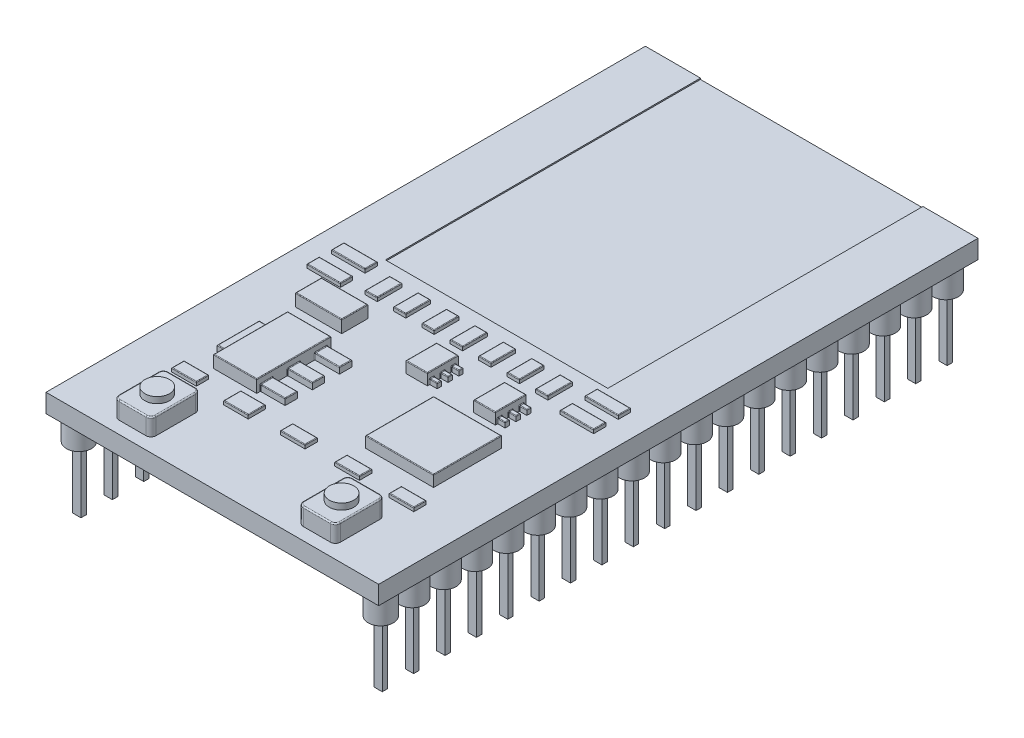
SolidWorks part; units mm, degrees
other "Markup1"
sketch "Sketch18" plane through (14.25, -8, 25.25) normal (0.0351, -0.9994, 0.0068) x (-0.8094, -0.0324, -0.5863)
sketch "Sketch19" plane through (14.25, -8, 25.25) normal (0.0351, -0.9994, 0.0068) x (-0.8094, -0.0324, -0.5863)
ref_plane "Alzado" through (0, 0, 0) normal (0, 0, 1) x (1, 0, 0)
ref_plane "Planta" through (0, 0, 0) normal (0, 1, 0) x (1, 0, 0)
ref_plane "Vista lateral" through (0, 0, 0) normal (1, 0, 0) x (0, 0, -1)
sketch "Sketch1" plane through (0, 0, 0) normal (0, 1, 0) x (1, 0, 0)
  line L0 (0, 0) -> (0, 24.257) construction
  line L1 (13.462, -24.257) -> (-13.462, -24.257)
  line L2 (13.462, -24.257) -> (13.462, 24.257)
  line L3 (13.462, 24.257) -> (-13.462, 24.257)
  line L4 (-13.462, -24.257) -> (-13.462, 24.257)
  line L5 (13.462, -24.257) -> (-13.462, 24.257) construction
  line L6 (13.462, 24.257) -> (-13.462, -24.257) construction
  line L7 (13.462, 0) -> (-13.462, 0) construction
  line L12 (11.462, 24.257) -> (11.462, 22.257) construction
  point P0 (0, 0)
  point P6 (13.462, 23.257)
  point P7 (12.462, 24.257)
  point P8 (17.05, 25.3)
  point P29 (11.462, 24.257)
  point P30 (-13.462, 24.257)
  point P31 (13.462, 24.257)
  point P32 (13.462, -24.257)
  point P33 (-13.462, -24.257)
  dimension "D1" = 48.514
  dimension "D2" = 26.924
  dimension "D3" = 1
  dimension "D4" = 1
  dimension "D6" = 2
  dimension "D7" = 2
extrude "Boss-Extrude1" add sketch "Sketch1" along normal blind 1.5 contours L1 L2 L3 L4 region at (0, 0, 0)
sketch "Sketch2" plane through (0, 0, 0) normal (0, -1, 0) x (1, 0, 0)
  line L0 (0, -24.257) -> (0, 24.257) construction
  line L1 (13.462, -24.257) -> (-13.462, -24.257) construction
  line L2 (13.462, 24.257) -> (-13.462, 24.257) construction
  line L3 (13.462, 0) -> (-13.462, 0) construction
  line L4 (13.462, 24.257) -> (13.462, -24.257) construction
  line L5 (-13.462, 24.257) -> (-13.462, -24.257) construction
  line L6 (-12.962, -23.0261) -> (-12.962, 24.257) construction
  line L7 (-12.962, -23.0261) -> (-12.962, -24.257) construction
  line L8 (-12.812, -19.067) -> (-12.712, -18.967)
  line L9 (-13.112, -18.567) -> (-12.812, -18.567)
  line L10 (-13.212, -18.667) -> (-13.212, -18.967)
  line L11 (-13.112, -19.067) -> (-12.812, -19.067)
  line L12 (-12.712, -18.667) -> (-12.712, -18.967)
  line L13 (-13.212, -18.567) -> (-12.712, -19.067) construction
  line L14 (-13.212, -19.067) -> (-12.712, -18.567) construction
  line L15 (-13.212, -18.967) -> (-13.112, -19.067)
  line L16 (-13.212, -18.667) -> (-13.112, -18.567)
  line L17 (-12.812, -18.567) -> (-12.712, -18.667)
  line L18 (-13.212, -16.427) -> (-13.112, -16.527)
  line L19 (-13.112, -16.527) -> (-12.812, -16.527)
  line L20 (-12.812, -16.527) -> (-12.712, -16.427)
  line L21 (-12.712, -16.127) -> (-12.712, -16.427)
  line L22 (-12.812, -16.027) -> (-12.712, -16.127)
  line L23 (-13.112, -16.027) -> (-12.812, -16.027)
  line L24 (-13.212, -16.127) -> (-13.112, -16.027)
  line L25 (-13.212, -16.127) -> (-13.212, -16.427)
  line L26 (-13.212, -13.887) -> (-13.112, -13.987)
  line L27 (-13.112, -13.987) -> (-12.812, -13.987)
  line L28 (-12.812, -13.987) -> (-12.712, -13.887)
  line L29 (-12.712, -13.587) -> (-12.712, -13.887)
  line L30 (-12.812, -13.487) -> (-12.712, -13.587)
  line L31 (-13.112, -13.487) -> (-12.812, -13.487)
  line L32 (-13.212, -13.587) -> (-13.112, -13.487)
  line L33 (-13.212, -13.587) -> (-13.212, -13.887)
  line L34 (-13.212, -11.347) -> (-13.112, -11.447)
  line L35 (-13.112, -11.447) -> (-12.812, -11.447)
  line L36 (-12.812, -11.447) -> (-12.712, -11.347)
  line L37 (-12.712, -11.047) -> (-12.712, -11.347)
  line L38 (-12.812, -10.947) -> (-12.712, -11.047)
  line L39 (-13.112, -10.947) -> (-12.812, -10.947)
  line L40 (-13.212, -11.047) -> (-13.112, -10.947)
  line L41 (-13.212, -11.047) -> (-13.212, -11.347)
  line L42 (-13.212, -8.807) -> (-13.112, -8.907)
  line L43 (-13.112, -8.907) -> (-12.812, -8.907)
  line L44 (-12.812, -8.907) -> (-12.712, -8.807)
  line L45 (-12.712, -8.507) -> (-12.712, -8.807)
  line L46 (-12.812, -8.407) -> (-12.712, -8.507)
  line L47 (-13.112, -8.407) -> (-12.812, -8.407)
  line L48 (-13.212, -8.507) -> (-13.112, -8.407)
  line L49 (-13.212, -8.507) -> (-13.212, -8.807)
  line L50 (-13.212, -6.267) -> (-13.112, -6.367)
  line L51 (-13.112, -6.367) -> (-12.812, -6.367)
  line L52 (-12.812, -6.367) -> (-12.712, -6.267)
  line L53 (-12.712, -5.967) -> (-12.712, -6.267)
  line L54 (-12.812, -5.867) -> (-12.712, -5.967)
  line L55 (-13.112, -5.867) -> (-12.812, -5.867)
  line L56 (-13.212, -5.967) -> (-13.112, -5.867)
  line L57 (-13.212, -5.967) -> (-13.212, -6.267)
  line L58 (-13.212, -3.727) -> (-13.112, -3.827)
  line L59 (-13.112, -3.827) -> (-12.812, -3.827)
  line L60 (-12.812, -3.827) -> (-12.712, -3.727)
  line L61 (-12.712, -3.427) -> (-12.712, -3.727)
  line L62 (-12.812, -3.327) -> (-12.712, -3.427)
  line L63 (-13.112, -3.327) -> (-12.812, -3.327)
  line L64 (-13.212, -3.427) -> (-13.112, -3.327)
  line L65 (-13.212, -3.427) -> (-13.212, -3.727)
  line L66 (-13.212, -1.187) -> (-13.112, -1.287)
  line L67 (-13.112, -1.287) -> (-12.812, -1.287)
  line L68 (-12.812, -1.287) -> (-12.712, -1.187)
  line L69 (-12.712, -0.887) -> (-12.712, -1.187)
  line L70 (-12.812, -0.787) -> (-12.712, -0.887)
  line L71 (-13.112, -0.787) -> (-12.812, -0.787)
  line L72 (-13.212, -0.887) -> (-13.112, -0.787)
  line L73 (-13.212, -0.887) -> (-13.212, -1.187)
  line L74 (-13.212, 1.353) -> (-13.112, 1.253)
  line L75 (-13.112, 1.253) -> (-12.812, 1.253)
  line L76 (-12.812, 1.253) -> (-12.712, 1.353)
  line L77 (-12.712, 1.653) -> (-12.712, 1.353)
  line L78 (-12.812, 1.753) -> (-12.712, 1.653)
  line L79 (-13.112, 1.753) -> (-12.812, 1.753)
  line L80 (-13.212, 1.653) -> (-13.112, 1.753)
  line L81 (-13.212, 1.653) -> (-13.212, 1.353)
  line L82 (-13.212, 3.893) -> (-13.112, 3.793)
  line L83 (-13.112, 3.793) -> (-12.812, 3.793)
  line L84 (-12.812, 3.793) -> (-12.712, 3.893)
  line L85 (-12.712, 4.193) -> (-12.712, 3.893)
  line L86 (-12.812, 4.293) -> (-12.712, 4.193)
  line L87 (-13.112, 4.293) -> (-12.812, 4.293)
  line L88 (-13.212, 4.193) -> (-13.112, 4.293)
  line L89 (-13.212, 4.193) -> (-13.212, 3.893)
  line L90 (-13.212, 6.433) -> (-13.112, 6.333)
  line L91 (-13.112, 6.333) -> (-12.812, 6.333)
  line L92 (-12.812, 6.333) -> (-12.712, 6.433)
  line L93 (-12.712, 6.733) -> (-12.712, 6.433)
  line L94 (-12.812, 6.833) -> (-12.712, 6.733)
  line L95 (-13.112, 6.833) -> (-12.812, 6.833)
  line L96 (-13.212, 6.733) -> (-13.112, 6.833)
  line L97 (-13.212, 6.733) -> (-13.212, 6.433)
  line L98 (-13.212, 8.973) -> (-13.112, 8.873)
  line L99 (-13.112, 8.873) -> (-12.812, 8.873)
  line L100 (-12.812, 8.873) -> (-12.712, 8.973)
  line L101 (-12.712, 9.273) -> (-12.712, 8.973)
  line L102 (-12.812, 9.373) -> (-12.712, 9.273)
  line L103 (-13.112, 9.373) -> (-12.812, 9.373)
  line L104 (-13.212, 9.273) -> (-13.112, 9.373)
  line L105 (-13.212, 9.273) -> (-13.212, 8.973)
  line L106 (-13.212, 11.513) -> (-13.112, 11.413)
  line L107 (-13.112, 11.413) -> (-12.812, 11.413)
  line L108 (-12.812, 11.413) -> (-12.712, 11.513)
  line L109 (-12.712, 11.813) -> (-12.712, 11.513)
  line L110 (-12.812, 11.913) -> (-12.712, 11.813)
  line L111 (-13.112, 11.913) -> (-12.812, 11.913)
  line L112 (-13.212, 11.813) -> (-13.112, 11.913)
  line L113 (-13.212, 11.813) -> (-13.212, 11.513)
  line L114 (-13.212, 14.053) -> (-13.112, 13.953)
  line L115 (-13.112, 13.953) -> (-12.812, 13.953)
  line L116 (-12.812, 13.953) -> (-12.712, 14.053)
  line L117 (-12.712, 14.353) -> (-12.712, 14.053)
  line L118 (-12.812, 14.453) -> (-12.712, 14.353)
  line L119 (-13.112, 14.453) -> (-12.812, 14.453)
  line L120 (-13.212, 14.353) -> (-13.112, 14.453)
  line L121 (-13.212, 14.353) -> (-13.212, 14.053)
  line L122 (-13.212, 16.593) -> (-13.112, 16.493)
  line L123 (-13.112, 16.493) -> (-12.812, 16.493)
  line L124 (-12.812, 16.493) -> (-12.712, 16.593)
  line L125 (-12.712, 16.893) -> (-12.712, 16.593)
  line L126 (-12.812, 16.993) -> (-12.712, 16.893)
  line L127 (-13.112, 16.993) -> (-12.812, 16.993)
  line L128 (-13.212, 16.893) -> (-13.112, 16.993)
  line L129 (-13.212, 16.893) -> (-13.212, 16.593)
  line L130 (12.812, 16.493) -> (12.712, 16.593)
  line L131 (12.712, 16.893) -> (12.712, 16.593)
  line L132 (12.812, 16.993) -> (12.712, 16.893)
  line L133 (13.112, 16.993) -> (12.812, 16.993)
  line L134 (13.212, 16.893) -> (13.112, 16.993)
  line L135 (13.212, 16.893) -> (13.212, 16.593)
  line L136 (13.212, 16.593) -> (13.112, 16.493)
  line L137 (13.112, 16.493) -> (12.812, 16.493)
  line L138 (13.212, 14.353) -> (13.212, 14.053)
  line L139 (13.212, 14.053) -> (13.112, 13.953)
  line L140 (13.112, 13.953) -> (12.812, 13.953)
  line L141 (12.812, 13.953) -> (12.712, 14.053)
  line L142 (12.712, 14.353) -> (12.712, 14.053)
  line L143 (12.812, 14.453) -> (12.712, 14.353)
  line L144 (13.112, 14.453) -> (12.812, 14.453)
  line L145 (13.212, 14.353) -> (13.112, 14.453)
  line L146 (13.212, 11.813) -> (13.212, 11.513)
  line L147 (13.212, 11.513) -> (13.112, 11.413)
  line L148 (13.112, 11.413) -> (12.812, 11.413)
  line L149 (12.812, 11.413) -> (12.712, 11.513)
  line L150 (12.712, 11.813) -> (12.712, 11.513)
  line L151 (12.812, 11.913) -> (12.712, 11.813)
  line L152 (13.112, 11.913) -> (12.812, 11.913)
  line L153 (13.212, 11.813) -> (13.112, 11.913)
  line L154 (13.212, 9.273) -> (13.212, 8.973)
  line L155 (13.212, 8.973) -> (13.112, 8.873)
  line L156 (13.112, 8.873) -> (12.812, 8.873)
  line L157 (12.812, 8.873) -> (12.712, 8.973)
  line L158 (12.712, 9.273) -> (12.712, 8.973)
  line L159 (12.812, 9.373) -> (12.712, 9.273)
  line L160 (13.112, 9.373) -> (12.812, 9.373)
  line L161 (13.212, 9.273) -> (13.112, 9.373)
  line L162 (13.212, 6.733) -> (13.212, 6.433)
  line L163 (13.212, 6.433) -> (13.112, 6.333)
  line L164 (13.112, 6.333) -> (12.812, 6.333)
  line L165 (12.812, 6.333) -> (12.712, 6.433)
  line L166 (12.712, 6.733) -> (12.712, 6.433)
  line L167 (12.812, 6.833) -> (12.712, 6.733)
  line L168 (13.112, 6.833) -> (12.812, 6.833)
  line L169 (13.212, 6.733) -> (13.112, 6.833)
  line L170 (13.212, 4.193) -> (13.212, 3.893)
  line L171 (13.212, 3.893) -> (13.112, 3.793)
  line L172 (13.112, 3.793) -> (12.812, 3.793)
  line L173 (12.812, 3.793) -> (12.712, 3.893)
  line L174 (12.712, 4.193) -> (12.712, 3.893)
  line L175 (12.812, 4.293) -> (12.712, 4.193)
  line L176 (13.112, 4.293) -> (12.812, 4.293)
  line L177 (13.212, 4.193) -> (13.112, 4.293)
  line L178 (13.212, 1.653) -> (13.212, 1.353)
  line L179 (13.212, 1.353) -> (13.112, 1.253)
  line L180 (13.112, 1.253) -> (12.812, 1.253)
  line L181 (12.812, 1.253) -> (12.712, 1.353)
  line L182 (12.712, 1.653) -> (12.712, 1.353)
  line L183 (12.812, 1.753) -> (12.712, 1.653)
  line L184 (13.112, 1.753) -> (12.812, 1.753)
  line L185 (13.212, 1.653) -> (13.112, 1.753)
  line L186 (13.212, -0.887) -> (13.212, -1.187)
  line L187 (13.212, -1.187) -> (13.112, -1.287)
  line L188 (13.112, -1.287) -> (12.812, -1.287)
  line L189 (12.812, -1.287) -> (12.712, -1.187)
  line L190 (12.712, -0.887) -> (12.712, -1.187)
  line L191 (12.812, -0.787) -> (12.712, -0.887)
  line L192 (13.112, -0.787) -> (12.812, -0.787)
  line L193 (13.212, -0.887) -> (13.112, -0.787)
  line L194 (13.212, -3.427) -> (13.212, -3.727)
  line L195 (13.212, -3.727) -> (13.112, -3.827)
  line L196 (13.112, -3.827) -> (12.812, -3.827)
  line L197 (12.812, -3.827) -> (12.712, -3.727)
  line L198 (12.712, -3.427) -> (12.712, -3.727)
  line L199 (12.812, -3.327) -> (12.712, -3.427)
  line L200 (13.112, -3.327) -> (12.812, -3.327)
  line L201 (13.212, -3.427) -> (13.112, -3.327)
  line L202 (13.212, -5.967) -> (13.212, -6.267)
  line L203 (13.212, -6.267) -> (13.112, -6.367)
  line L204 (13.112, -6.367) -> (12.812, -6.367)
  line L205 (12.812, -6.367) -> (12.712, -6.267)
  line L206 (12.712, -5.967) -> (12.712, -6.267)
  line L207 (12.812, -5.867) -> (12.712, -5.967)
  line L208 (13.112, -5.867) -> (12.812, -5.867)
  line L209 (13.212, -5.967) -> (13.112, -5.867)
  line L210 (13.212, -8.507) -> (13.212, -8.807)
  line L211 (13.212, -8.807) -> (13.112, -8.907)
  line L212 (13.112, -8.907) -> (12.812, -8.907)
  line L213 (12.812, -8.907) -> (12.712, -8.807)
  line L214 (12.712, -8.507) -> (12.712, -8.807)
  line L215 (12.812, -8.407) -> (12.712, -8.507)
  line L216 (13.112, -8.407) -> (12.812, -8.407)
  line L217 (13.212, -8.507) -> (13.112, -8.407)
  line L218 (13.212, -11.047) -> (13.212, -11.347)
  line L219 (13.212, -11.347) -> (13.112, -11.447)
  line L220 (13.112, -11.447) -> (12.812, -11.447)
  line L221 (12.812, -11.447) -> (12.712, -11.347)
  line L222 (12.712, -11.047) -> (12.712, -11.347)
  line L223 (12.812, -10.947) -> (12.712, -11.047)
  line L224 (13.112, -10.947) -> (12.812, -10.947)
  line L225 (13.212, -11.047) -> (13.112, -10.947)
  line L226 (13.212, -13.587) -> (13.212, -13.887)
  line L227 (13.212, -13.887) -> (13.112, -13.987)
  line L228 (13.112, -13.987) -> (12.812, -13.987)
  line L229 (12.812, -13.987) -> (12.712, -13.887)
  line L230 (12.712, -13.587) -> (12.712, -13.887)
  line L231 (12.812, -13.487) -> (12.712, -13.587)
  line L232 (13.112, -13.487) -> (12.812, -13.487)
  line L233 (13.212, -13.587) -> (13.112, -13.487)
  line L234 (13.212, -16.127) -> (13.212, -16.427)
  line L235 (13.212, -16.427) -> (13.112, -16.527)
  line L236 (13.112, -16.527) -> (12.812, -16.527)
  line L237 (12.812, -16.527) -> (12.712, -16.427)
  line L238 (12.712, -16.127) -> (12.712, -16.427)
  line L239 (12.812, -16.027) -> (12.712, -16.127)
  line L240 (13.112, -16.027) -> (12.812, -16.027)
  line L241 (13.212, -16.127) -> (13.112, -16.027)
  line L242 (13.212, -18.667) -> (13.212, -18.967)
  line L243 (13.212, -18.967) -> (13.112, -19.067)
  line L244 (13.112, -19.067) -> (12.812, -19.067)
  line L245 (12.812, -19.067) -> (12.712, -18.967)
  line L246 (12.712, -18.667) -> (12.712, -18.967)
  line L247 (12.812, -18.567) -> (12.712, -18.667)
  line L248 (13.112, -18.567) -> (12.812, -18.567)
  line L249 (13.212, -18.667) -> (13.112, -18.567)
  point P12 (-14.25, -25.25)
  point P13 (-13.462, -21.6118)
  point P14 (-12.962, -23.0261)
  point P18 (-12.962, -18.817)
  point P19 (-12.962, -18.817)
  dimension "D1" = 1.5
  dimension "D2" = 5.44
  dimension "D3" = 0.5
  dimension "D4" = 0.5
  dimension "D5" = 15
  dimension "D6" = 15
sketch "Sketch5" plane through (0, 1.5, 0) normal (0, 1, 0) x (1, 0, 0)
  line L0 (-13.462, -23.257) -> (-8.962, -23.257) construction
  line L1 (0, -24.257) -> (0, 24.257) construction
  line L2 (-8.562, -23.257) -> (-6.362, -23.257)
  line L3 (-8.962, -22.857) -> (-8.962, -19.657)
  line L4 (-8.562, -19.257) -> (-6.362, -19.257)
  line L5 (-5.962, -22.857) -> (-5.962, -19.657)
  line L6 (13.462, -24.257) -> (-13.462, -24.257) construction
  line L7 (13.462, 24.257) -> (-13.462, 24.257) construction
  line L8 (5.962, -22.857) -> (5.962, -19.657)
  line L9 (8.562, -23.257) -> (6.362, -23.257)
  line L10 (8.962, -22.857) -> (8.962, -19.657)
  line L11 (8.562, -19.257) -> (6.362, -19.257)
  arc A0 (-8.962, -22.857) -> (-8.562, -23.257) centre (-8.562, -22.857) ccw
  arc A1 (-6.362, -23.257) -> (-5.962, -22.857) centre (-6.362, -22.857) ccw
  arc A2 (-6.362, -19.257) -> (-5.962, -19.657) centre (-6.362, -19.657) cw
  arc A3 (-8.962, -19.657) -> (-8.562, -19.257) centre (-8.562, -19.657) cw
  arc A4 (6.362, -23.257) -> (5.962, -22.857) centre (6.362, -22.857) cw
  arc A5 (8.962, -22.857) -> (8.562, -23.257) centre (8.562, -22.857) cw
  arc A6 (8.962, -19.657) -> (8.562, -19.257) centre (8.562, -19.657) ccw
  arc A7 (6.362, -19.257) -> (5.962, -19.657) centre (6.362, -19.657) ccw
  point P11 (-5.962, -23.257)
  point P14 (-5.962, -19.257)
  point P17 (-8.962, -19.257)
  point P36 (0, 0)
  dimension "D4" = 0.4
  dimension "D1" = 4.5
  dimension "D2" = 4
  dimension "D3" = 3
extrude "Boss-Extrude5" add sketch "Sketch5" along normal blind 1.4
sketch "Sketch6" plane through (0, 2.9, 0) normal (0, 1, 0) x (1, 0, 0)
  line L0 (-8.962, -21.257) -> (-5.962, -21.257) construction
  line L1 (-8.962, -19.657) -> (-8.962, -22.857) construction
  line L2 (-5.962, -22.857) -> (-5.962, -19.657) construction
  line L3 (0, -24.257) -> (0, 24.257) construction
  line L4 (13.462, -24.257) -> (-13.462, -24.257) construction
  line L5 (13.462, 24.257) -> (-13.462, 24.257) construction
  circle A0 centre (-7.462, -21.257) radius 0.9958
  circle A1 centre (7.462, -21.257) radius 0.9958
extrude "Boss-Extrude6" add sketch "Sketch6" along normal blind 0.5
sketch "Sketch7" plane through (0, 1.5, 0) normal (0, 1, 0) x (1, 0, 0)
  line L0 (13.462, 24.257) -> (-13.462, 24.257) construction
  line L1 (0, 24.257) -> (0, 0) construction
  line L3 (-9, 24.257) -> (9, 24.257)
  line L4 (-9, 24.257) -> (-9, -1.243)
  line L5 (-9, -1.243) -> (9, -1.243)
  line L6 (9, 24.257) -> (9, -1.243)
  point P0 (0, 24.257)
  point P5 (-9, 24.257)
  dimension "D1" = 9
  dimension "D2" = 18
  dimension "D3" = 25.5
extrude "Cut-Extrude1" cut sketch "Sketch7" against normal blind 0.1
sketch "Sketch8" plane through (0, 1.5, 0) normal (0, 1, 0) x (1, 0, 0)
  line L0 (13.462, -24.257) -> (-13.462, -24.257) construction
  line L1 (0, -24.257) -> (0, 0) construction
  line L2 (2.8, -4.5) -> (2.8, -2.5)
  line L3 (0.5, -4.5) -> (-0.5, -4.5)
  line L4 (1, -17.75) -> (-1, -17.75)
  line L5 (1, -17.75) -> (1, -16.75)
  line L6 (1, -16.75) -> (-1, -16.75)
  line L7 (-1, -17.75) -> (-1, -16.75)
  line L8 (1, -17.75) -> (-1, -16.75) construction
  line L9 (1, -16.75) -> (-1, -17.75) construction
  line L10 (-3.4, -17.95) -> (-5.4, -17.95)
  line L11 (-3.4, -17.95) -> (-3.4, -16.55)
  line L12 (-3.4, -16.55) -> (-5.4, -16.55)
  line L13 (-5.4, -17.95) -> (-5.4, -16.55)
  line L14 (-3.4, -17.95) -> (-5.4, -16.55) construction
  line L15 (-3.4, -16.55) -> (-5.4, -17.95) construction
  line L16 (-9.8, -17.75) -> (-7.8, -17.75)
  line L17 (-9.8, -17.75) -> (-9.8, -16.75)
  line L18 (-9.8, -16.75) -> (-7.8, -16.75)
  line L19 (-7.8, -17.75) -> (-7.8, -16.75)
  line L20 (-9.8, -17.75) -> (-7.8, -16.75) construction
  line L21 (-9.8, -16.75) -> (-7.8, -17.75) construction
  line L22 (5.4, -17.75) -> (3.4, -17.75)
  line L23 (5.4, -17.75) -> (5.4, -16.75)
  line L24 (5.4, -16.75) -> (3.4, -16.75)
  line L25 (3.4, -17.75) -> (3.4, -16.75)
  line L26 (5.4, -17.75) -> (3.4, -16.75) construction
  line L27 (5.4, -16.75) -> (3.4, -17.75) construction
  line L28 (9.8, -17.75) -> (7.8, -17.75)
  line L29 (9.8, -17.75) -> (9.8, -16.75)
  line L30 (9.8, -16.75) -> (7.8, -16.75)
  line L31 (7.8, -17.75) -> (7.8, -16.75)
  line L32 (9.8, -17.75) -> (7.8, -16.75) construction
  line L33 (9.8, -16.75) -> (7.8, -17.75) construction
  line L34 (0.5, -4.5) -> (0.5, -2.5)
  line L35 (0.5, -2.5) -> (-0.5, -2.5)
  line L36 (-0.5, -4.5) -> (-0.5, -2.5)
  line L37 (0.5, -4.5) -> (-0.5, -2.5) construction
  line L38 (0.5, -2.5) -> (-0.5, -4.5) construction
  line L39 (2.8, -2.5) -> (1.8, -2.5)
  line L40 (1.8, -4.5) -> (1.8, -2.5)
  line L41 (2.8, -4.5) -> (1.8, -4.5)
  line L42 (5.1, -4.5) -> (5.1, -2.5)
  line L43 (5.1, -2.5) -> (4.1, -2.5)
  line L44 (4.1, -4.5) -> (4.1, -2.5)
  line L45 (5.1, -4.5) -> (4.1, -4.5)
  line L46 (7.4, -4.5) -> (7.4, -2.5)
  line L47 (7.4, -2.5) -> (6.4, -2.5)
  line L48 (6.4, -4.5) -> (6.4, -2.5)
  line L49 (7.4, -4.5) -> (6.4, -4.5)
  line L50 (-7.4, -4.5) -> (-6.4, -4.5)
  line L51 (-6.4, -4.5) -> (-6.4, -2.5)
  line L52 (-7.4, -2.5) -> (-6.4, -2.5)
  line L53 (-7.4, -4.5) -> (-7.4, -2.5)
  line L54 (-5.1, -4.5) -> (-4.1, -4.5)
  line L55 (-4.1, -4.5) -> (-4.1, -2.5)
  line L56 (-5.1, -2.5) -> (-4.1, -2.5)
  line L57 (-5.1, -4.5) -> (-5.1, -2.5)
  line L58 (-2.8, -4.5) -> (-1.8, -4.5)
  line L59 (-1.8, -4.5) -> (-1.8, -2.5)
  line L60 (-2.8, -2.5) -> (-1.8, -2.5)
  line L61 (-2.8, -4.5) -> (-2.8, -2.5)
  line L62 (7.4, -3.5) -> (13.462, -3.5) construction
  line L63 (13.462, -24.257) -> (13.462, 24.257) construction
  line L64 (11.6049, -3) -> (11.6049, -2)
  line L65 (11.6049, -5) -> (8.8951, -5)
  line L66 (11.6049, -5) -> (11.6049, -4)
  line L67 (11.6049, -2) -> (8.8951, -2)
  line L68 (8.8951, -5) -> (8.8951, -4)
  line L69 (11.6049, -5) -> (8.8951, -2) construction
  line L70 (11.6049, -2) -> (8.8951, -5) construction
  line L71 (11.6049, -4) -> (8.8951, -4)
  line L72 (8.8951, -3) -> (8.8951, -2)
  line L73 (11.6049, -3) -> (8.8951, -3)
  line L74 (-11.6049, -5) -> (-8.8951, -5)
  line L75 (11.6049, -4) -> (8.8951, -3) construction
  line L76 (11.6049, -3) -> (8.8951, -4) construction
  line L77 (-8.8951, -5) -> (-8.8951, -4)
  line L78 (-11.6049, -4) -> (-8.8951, -4)
  line L79 (-11.6049, -5) -> (-11.6049, -4)
  line L80 (-11.6049, -3) -> (-11.6049, -2)
  line L81 (-11.6049, -3) -> (-8.8951, -3)
  line L82 (-8.8951, -3) -> (-8.8951, -2)
  line L83 (-11.6049, -2) -> (-8.8951, -2)
  point P0 (0, -24.257)
  point P6 (0, -17.25)
  point P7 (-4.4, -17.25)
  point P8 (-8.8, -17.25)
  point P9 (-4.4, -17.25)
  point P10 (0, -17.25)
  point P17 (4.4, -17.25)
  point P18 (8.8, -17.25)
  point P21 (-8.8, -17.25)
  point P26 (4.4, -17.25)
  point P31 (8.8, -17.25)
  point P36 (0, -3.5)
  point P37 (0, -3.5)
  point P70 (10.25, -3.5)
  point P71 (10.25, -3.5)
  point P76 (10.25, -3.5)
  dimension "D1" = 3
  dimension "D2" = 2
  dimension "D3" = 1
  dimension "D4" = 2
  dimension "D5" = 1.4
  dimension "D6" = 2
  dimension "D7" = 1
  dimension "D8" = 2
  dimension "D9" = 2
  dimension "D11" = 1
extrude "Boss-Extrude7" add sketch "Sketch8" along normal blind 0.3
sketch "Sketch9" plane through (0, 1.5, 0) normal (0, 1, 0) x (1, 0, 0)
  line L0 (3.4, -16.75) -> (3.4, -1.243) construction
  line L1 (-9, -1.243) -> (9, -1.243) construction
  line L2 (5.1, -4.5) -> (6.4, -4.5) construction
  line L3 (3.4, -15.25) -> (8.9, -15.25)
  line L4 (3.4, -15.25) -> (3.4, -9.75)
  line L5 (3.4, -9.75) -> (8.9, -9.75)
  line L6 (8.9, -15.25) -> (8.9, -9.75)
  line L7 (6.15, -9.75) -> (6.15, -4.5) construction
  line L8 (-0.225, -8.375) -> (-0.225, -5.875)
  line L9 (7.025, -8.375) -> (5.275, -8.375)
  line L10 (7.025, -8.375) -> (7.025, -5.875)
  line L11 (7.025, -5.875) -> (5.275, -5.875)
  line L12 (5.275, -8.375) -> (5.275, -5.875)
  line L13 (7.025, -8.375) -> (5.275, -5.875) construction
  line L14 (7.025, -5.875) -> (5.275, -8.375) construction
  line L15 (-0.225, -8.375) -> (1.525, -8.375)
  line L16 (1.525, -8.375) -> (1.525, -5.875)
  line L17 (-0.225, -5.875) -> (1.525, -5.875)
  point P5 (3.4, -15.25)
  point P16 (6.15, -7.125)
  point P17 (6.15, -7.125)
  dimension "D1" = 1.75
  dimension "D2" = 1.5
  dimension "D3" = 5.5
  dimension "D4" = 2.5
  dimension "D5" = 5.5
extrude "Boss-Extrude8" add sketch "Sketch9" along normal blind 0.9
sketch "Sketch10" plane through (0, 1.5, 0) normal (0, 1, 0) x (1, 0, 0)
  line L0 (-9.8, -17.25) -> (-3.4, -17.25) construction
  line L1 (-9.8, -16.75) -> (-9.8, -17.75) construction
  line L2 (-3.4, -17.95) -> (-3.4, -16.55) construction
  line L3 (-0.225, -8.375) -> (-13.462, -8.375) construction
  line L4 (-13.462, -24.257) -> (-13.462, 24.257) construction
  line L5 (-6.6, -17.25) -> (-6.6, -8.375) construction
  line L7 (-4.85, -15.8125) -> (-8.35, -15.8125)
  line L8 (-4.85, -15.8125) -> (-4.85, -9.8125)
  line L9 (-4.85, -9.8125) -> (-8.35, -9.8125)
  line L10 (-8.35, -15.8125) -> (-8.35, -9.8125)
  line L11 (-4.85, -15.8125) -> (-8.35, -9.8125) construction
  line L12 (-4.85, -9.8125) -> (-8.35, -15.8125) construction
  point P13 (-6.6, -12.8125)
  dimension "D1" = 6
  dimension "D2" = 3.5
extrude "Boss-Extrude9" add sketch "Sketch10" along normal blind 1
sketch "Sketch11" plane through (0, 1.5, 0) normal (0, 1, 0) x (1, 0, 0)
  line L0 (-4.85, -12.8125) -> (-8.35, -12.8125) construction
  line L1 (-4.85, -15.8125) -> (-4.85, -9.8125) construction
  line L2 (-8.35, -9.8125) -> (-8.35, -15.8125) construction
  line L3 (-4.85, -12.8125) -> (-4.85, -11.1125) construction
  line L4 (-4.85, -15.8125) -> (-4.85, -9.8125) construction
  line L5 (-4.85, -12.3125) -> (-2.85, -12.3125)
  line L6 (-4.85, -11.1125) -> (-2.85, -11.1125)
  line L7 (-4.85, -11.1125) -> (-4.85, -10.1125)
  line L8 (-4.85, -10.1125) -> (-2.85, -10.1125)
  line L9 (-2.85, -11.1125) -> (-2.85, -10.1125)
  line L10 (-2.85, -13.3125) -> (-2.85, -12.3125)
  line L11 (-4.85, -13.3125) -> (-4.85, -12.3125)
  line L12 (-4.85, -13.3125) -> (-2.85, -13.3125)
  line L13 (-4.85, -14.5125) -> (-2.85, -14.5125)
  line L14 (-2.85, -15.5125) -> (-2.85, -14.5125)
  line L15 (-4.85, -15.5125) -> (-4.85, -14.5125)
  line L16 (-4.85, -15.5125) -> (-2.85, -15.5125)
  line L17 (-4.85, -14.5125) -> (-8.35, -14.5125) construction
  line L18 (-8.35, -9.8125) -> (-8.35, -15.8125) construction
  line L20 (-8.35, -14.5125) -> (-9.35, -14.5125)
  line L21 (-8.35, -14.5125) -> (-8.35, -11.1125)
  line L22 (-8.35, -11.1125) -> (-9.35, -11.1125)
  line L23 (-9.35, -14.5125) -> (-9.35, -11.1125)
  dimension "D1" = 1
  dimension "D2" = 2
  dimension "D3" = 1
  dimension "D4" = 3
extrude "Boss-Extrude10" add sketch "Sketch11" along normal blind 0.5
sketch "Sketch12" plane through (0, 1.5, 0) normal (0, 1, 0) x (1, 0, 0)
  line L0 (7.025, -7.125) -> (5.275, -7.125) construction
  line L1 (7.025, -8.375) -> (7.025, -5.875) construction
  line L2 (5.275, -5.875) -> (5.275, -8.375) construction
  line L3 (7.025, -7.125) -> (7.025, -6.425) construction
  line L4 (7.025, -7.305) -> (7.625, -7.305)
  line L5 (7.025, -6.425) -> (7.625, -6.425)
  line L6 (7.025, -6.425) -> (7.025, -6.075)
  line L7 (7.025, -6.075) -> (7.625, -6.075)
  line L8 (7.625, -6.425) -> (7.625, -6.075)
  line L9 (7.025, -7.305) -> (7.025, -6.955)
  line L10 (7.025, -6.955) -> (7.625, -6.955)
  line L11 (7.625, -7.305) -> (7.625, -6.955)
  line L12 (7.025, -8.185) -> (7.625, -8.185)
  line L13 (7.025, -8.185) -> (7.025, -7.835)
  line L14 (7.025, -7.835) -> (7.625, -7.835)
  line L15 (7.625, -8.185) -> (7.625, -7.835)
  line L16 (1.525, -7.125) -> (-0.225, -7.125) construction
  line L17 (1.525, -8.375) -> (1.525, -5.875) construction
  line L18 (-0.225, -5.875) -> (-0.225, -8.375) construction
  line L19 (1.525, -7.125) -> (1.525, -6.425) construction
  line L20 (1.525, -6.955) -> (2.125, -6.955)
  line L21 (1.525, -6.425) -> (2.125, -6.425)
  line L22 (1.525, -6.425) -> (1.525, -6.075)
  line L23 (1.525, -6.075) -> (2.125, -6.075)
  line L24 (2.125, -6.425) -> (2.125, -6.075)
  line L25 (1.525, -7.305) -> (1.525, -6.955)
  line L26 (2.125, -7.305) -> (2.125, -6.955)
  line L27 (1.525, -7.305) -> (2.125, -7.305)
  line L28 (1.525, -7.835) -> (2.125, -7.835)
  line L29 (1.525, -8.185) -> (1.525, -7.835)
  line L30 (2.125, -8.185) -> (2.125, -7.835)
  line L31 (1.525, -8.185) -> (2.125, -8.185)
  line L32 (-0.225, -5.875) -> (-0.225, -8.375) construction
  line L33 (-0.225, -7.835) -> (-0.725, -7.835)
  line L34 (-0.225, -7.835) -> (-0.225, -6.425)
  line L35 (-0.225, -6.425) -> (-0.725, -6.425)
  line L36 (-0.725, -7.835) -> (-0.725, -6.425)
  line L37 (5.275, -5.875) -> (5.275, -8.375) construction
  line L38 (5.275, -7.835) -> (4.775, -7.835)
  line L39 (5.275, -7.835) -> (5.275, -6.425)
  line L40 (5.275, -6.425) -> (4.775, -6.425)
  line L41 (4.775, -7.835) -> (4.775, -6.425)
  dimension "D1" = 0.7
  dimension "D2" = 0.6
  dimension "D3" = 0.35
  dimension "D5" = 0.7
  dimension "D6" = 0.6
  dimension "D8" = 0.5
  dimension "D9" = 0.5
  dimension "D4" = 3
  dimension "D7" = 3
extrude "Boss-Extrude11" add sketch "Sketch12" along normal blind 0.4
sketch "Sketch13" plane through (0, 1.5, 0) normal (0, 1, 0) x (1, 0, 0)
  line L0 (1.525, -6.075) -> (-13.462, -6.075) construction
  line L1 (-13.462, -24.257) -> (-13.462, 24.257) construction
  line L2 (1.525, -8.185) -> (-13.462, -8.185) construction
  line L3 (-9.35, -11.1125) -> (-9.35, -8.185) construction
  line L4 (-8.35, -11.1125) -> (-9.35, -11.1125) construction
  line L6 (-9.35, -8.185) -> (-5.6, -8.185)
  line L7 (-9.35, -8.185) -> (-9.35, -6.075)
  line L8 (-9.35, -6.075) -> (-5.6, -6.075)
  line L9 (-5.6, -8.185) -> (-5.6, -6.075)
  dimension "D1" = 3.75
extrude "Boss-Extrude12" add sketch "Sketch13" along normal blind 1
fillet "Fillet8" radius 0.05 84 edges at (10.25, 1.8, 5) (8.8951, 1.8, 4.5) (10.25, 1.8, 4) (11.6049, 1.8, 4.5) (10.25, 1.8, 2) (11.6049, 1.8, 2.5) (10.25, 1.8, 3) (8.8951, 1.8, 2.5) (6.9, 1.8, 2.5) (7.4, 1.8, 3.5) (6.9, 1.8, 4.5) (6.4, 1.8, 3.5) (4.6, 1.8, 2.5) (5.1, 1.8, 3.5) (4.6, 1.8, 4.5) (4.1, 1.8, 3.5) (2.3, 1.8, 2.5) (2.8, 1.8, 3.5) (2.3, 1.8, 4.5) (1.8, 1.8, 3.5) (0, 1.8, 2.5) (0.5, 1.8, 3.5) (0, 1.8, 4.5) (-0.5, 1.8, 3.5) (-2.3, 1.8, 2.5) (-1.8, 1.8, 3.5) (-2.3, 1.8, 4.5) (-2.8, 1.8, 3.5) (-4.6, 1.8, 2.5) (-4.1, 1.8, 3.5) (-4.6, 1.8, 4.5) (-5.1, 1.8, 3.5) (-10.25, 1.8, 4) (-8.8951, 1.8, 4.5) (-10.25, 1.8, 5) (-11.6049, 1.8, 4.5) (-11.6049, 1.8, 2.5) (-10.25, 1.8, 2) (-8.8951, 1.8, 2.5) (-10.25, 1.8, 3) (-6.9, 1.8, 2.5) (-6.4, 1.8, 3.5) (-6.9, 1.8, 4.5) (-7.4, 1.8, 3.5) (-7.475, 2.5, 6.075) (-5.6, 2.5, 7.13) (-7.475, 2.5, 8.185) (-9.35, 2.5, 7.13) (-0.225, 2.4, 7.125) (0.65, 2.4, 5.875) (1.525, 2.4, 7.125) (0.65, 2.4, 8.375) (6.15, 2.4, 5.875) (7.025, 2.4, 7.125) (6.15, 2.4, 8.375) (5.275, 2.4, 7.125) (-6.6, 2.5, 9.8125) (-4.85, 2.5, 12.8125) (-6.6, 2.5, 15.8125) (-8.35, 2.5, 12.8125) (6.15, 2.4, 9.75) (8.9, 2.4, 12.5) (6.15, 2.4, 15.25) (3.4, 2.4, 12.5) (-8.8, 1.8, 17.75) (-9.8, 1.8, 17.25) (-8.8, 1.8, 16.75) (-7.8, 1.8, 17.25) (-4.4, 1.8, 16.55) (-3.4, 1.8, 17.25) (-4.4, 1.8, 17.95) (-5.4, 1.8, 17.25) (0, 1.8, 16.75) (1, 1.8, 17.25) (0, 1.8, 17.75) (-1, 1.8, 17.25) (4.4, 1.8, 16.75) (5.4, 1.8, 17.25) (4.4, 1.8, 17.75) (3.4, 1.8, 17.25) (8.8, 1.8, 16.75) (9.8, 1.8, 17.25) (8.8, 1.8, 17.75) (7.8, 1.8, 17.25)
fillet "Fillet9" radius 0.05 72 edges at (-0.225, 1.7, 7.835) (-0.225, 1.7, 6.425) (1.525, 1.7, 6.075) (1.525, 1.7, 6.425) (1.525, 1.7, 6.955) (1.525, 1.7, 7.305) (1.525, 1.7, 7.835) (1.525, 1.7, 8.185) (5.275, 1.7, 7.835) (5.275, 1.7, 6.425) (7.025, 1.7, 6.075) (7.025, 1.7, 6.425) (7.025, 1.7, 6.955) (7.025, 1.7, 7.305) (7.025, 1.7, 7.835) (7.025, 1.7, 8.185) (-4.85, 1.75, 15.5125) (-4.85, 1.75, 14.5125) (-4.85, 1.75, 11.1125) (-4.85, 1.75, 10.1125) (-4.85, 1.75, 13.3125) (-4.85, 1.75, 12.3125) (-8.35, 1.75, 14.5125) (-8.35, 1.75, 11.1125) (-0.475, 1.9, 7.835) (-0.725, 1.9, 7.13) (-0.475, 1.9, 6.425) (-0.225, 1.9, 7.13) (1.825, 1.9, 6.075) (2.125, 1.9, 6.25) (1.825, 1.9, 6.425) (1.525, 1.9, 6.25) (1.525, 1.9, 7.13) (1.825, 1.9, 6.955) (2.125, 1.9, 7.13) (1.825, 1.9, 7.305) (1.525, 1.9, 8.01) (1.825, 1.9, 7.835) (2.125, 1.9, 8.01) (1.825, 1.9, 8.185) (5.025, 1.9, 7.835) (4.775, 1.9, 7.13) (5.025, 1.9, 6.425) (5.275, 1.9, 7.13) (7.325, 1.9, 6.075) (7.625, 1.9, 6.25) (7.325, 1.9, 6.425) (7.025, 1.9, 6.25) (7.325, 1.9, 6.955) (7.625, 1.9, 7.13) (7.325, 1.9, 7.305) (7.025, 1.9, 7.13) (7.325, 1.9, 7.835) (7.625, 1.9, 8.01) (7.325, 1.9, 8.185) (7.025, 1.9, 8.01) (-3.85, 2, 15.5125) (-4.85, 2, 15.0125) (-3.85, 2, 14.5125) (-2.85, 2, 15.0125) (-3.85, 2, 11.1125) (-4.85, 2, 10.6125) (-3.85, 2, 10.1125) (-2.85, 2, 10.6125) (-3.85, 2, 13.3125) (-4.85, 2, 12.8125) (-3.85, 2, 12.3125) (-2.85, 2, 12.8125) (-8.85, 2, 14.5125) (-9.35, 2, 12.8125) (-8.85, 2, 11.1125) (-8.35, 2, 12.8125)
fillet "Fillet10" radius 0.1 16 edges at (-6.0792, 2.9, 19.3742) (-5.962, 2.9, 21.257) (-6.0792, 2.9, 23.1398) (-7.462, 2.9, 23.257) (-8.8448, 2.9, 23.1398) (-8.962, 2.9, 21.257) (-8.8448, 2.9, 19.3742) (8.8448, 2.9, 19.3742) (8.962, 2.9, 21.257) (8.8448, 2.9, 23.1398) (7.462, 2.9, 23.257) (6.0792, 2.9, 23.1398) (5.962, 2.9, 21.257) (6.0792, 2.9, 19.3742) (-7.462, 2.9, 19.257) (7.462, 2.9, 19.257)
sketch "Sketch14" plane through (0, 0, 0) normal (0, -1, 0) x (1, 0, 0)
  text T0 "A.Patiño" font "Century Gothic" height in points 8
sketch "Sketch15" plane through (0, 1.5, 0) normal (0, 1, 0) x (1, 0, 0)
  line L0 (13.462, -24.257) -> (-13.462, -24.257) construction
  line L1 (0, 0) -> (0, -24.257) construction
  line L2 (2.595, -24.257) -> (-2.595, -24.257)
  line L3 (2.595, -24.257) -> (2.595, -23.907) construction
  line L5 (2.595, -23.907) -> (0.735, -23.907)
  line L6 (2.595, -23.907) -> (2.595, -23.457)
  line L7 (2.595, -23.457) -> (0.735, -23.457)
  line L8 (0.735, -23.907) -> (0.735, -23.457)
  point P0 (0, -24.257)
  point P9 (0, -24.257)
  dimension "D1" = 5.19
  dimension "D2" = 0.35
  dimension "D3" = 0.45
  dimension "D4" = 1.86
sketch "Sketch23" plane through (0, 0, 0) normal (0, -1, 0) x (-1, 0, 0)
  line L0 (0, 24.257) -> (0, -24.257) construction
  line L1 (-13.462, 24.257) -> (13.462, 24.257) construction
  line L2 (11.912, -20.5993) -> (11.912, -19.9897)
  line L3 (12.5216, -23.1393) -> (11.912, -23.1393)
  line L4 (12.5216, -23.1393) -> (12.5216, -22.5297)
  line L5 (12.5216, -22.5297) -> (11.912, -22.5297)
  line L6 (11.912, -23.1393) -> (11.912, -22.5297)
  line L7 (12.5216, -23.1393) -> (11.912, -22.5297) construction
  line L8 (12.5216, -22.5297) -> (11.912, -23.1393) construction
  line L9 (12.5216, -20.5993) -> (11.912, -20.5993)
  line L10 (12.5216, -20.5993) -> (12.5216, -19.9897)
  line L11 (12.5216, -19.9897) -> (11.912, -19.9897)
  line L12 (11.912, -18.0593) -> (11.912, -17.4497)
  line L13 (12.5216, -18.0593) -> (11.912, -18.0593)
  line L14 (12.5216, -18.0593) -> (12.5216, -17.4497)
  line L15 (12.5216, -17.4497) -> (11.912, -17.4497)
  line L16 (11.912, -15.5193) -> (11.912, -14.9097)
  line L17 (12.5216, -15.5193) -> (11.912, -15.5193)
  line L18 (12.5216, -15.5193) -> (12.5216, -14.9097)
  line L19 (12.5216, -14.9097) -> (11.912, -14.9097)
  line L20 (11.912, -12.9793) -> (11.912, -12.3697)
  line L21 (12.5216, -12.9793) -> (11.912, -12.9793)
  line L22 (12.5216, -12.9793) -> (12.5216, -12.3697)
  line L23 (12.5216, -12.3697) -> (11.912, -12.3697)
  line L24 (11.912, -10.4393) -> (11.912, -9.8297)
  line L25 (12.5216, -10.4393) -> (11.912, -10.4393)
  line L26 (12.5216, -10.4393) -> (12.5216, -9.8297)
  line L27 (12.5216, -9.8297) -> (11.912, -9.8297)
  line L28 (11.912, -7.8993) -> (11.912, -7.2897)
  line L29 (12.5216, -7.8993) -> (11.912, -7.8993)
  line L30 (12.5216, -7.8993) -> (12.5216, -7.2897)
  line L31 (12.5216, -7.2897) -> (11.912, -7.2897)
  line L32 (11.912, -5.3593) -> (11.912, -4.7497)
  line L33 (12.5216, -5.3593) -> (11.912, -5.3593)
  line L34 (12.5216, -5.3593) -> (12.5216, -4.7497)
  line L35 (12.5216, -4.7497) -> (11.912, -4.7497)
  line L36 (11.912, -2.8193) -> (11.912, -2.2097)
  line L37 (12.5216, -2.8193) -> (11.912, -2.8193)
  line L38 (12.5216, -2.8193) -> (12.5216, -2.2097)
  line L39 (12.5216, -2.2097) -> (11.912, -2.2097)
  line L40 (11.912, -0.2793) -> (11.912, 0.3303)
  line L41 (12.5216, -0.2793) -> (11.912, -0.2793)
  line L42 (12.5216, -0.2793) -> (12.5216, 0.3303)
  line L43 (12.5216, 0.3303) -> (11.912, 0.3303)
  line L44 (11.912, 2.2607) -> (11.912, 2.8703)
  line L45 (12.5216, 2.2607) -> (11.912, 2.2607)
  line L46 (12.5216, 2.2607) -> (12.5216, 2.8703)
  line L47 (12.5216, 2.8703) -> (11.912, 2.8703)
  line L48 (11.912, 4.8007) -> (11.912, 5.4103)
  line L49 (12.5216, 4.8007) -> (11.912, 4.8007)
  line L50 (12.5216, 4.8007) -> (12.5216, 5.4103)
  line L51 (12.5216, 5.4103) -> (11.912, 5.4103)
  line L52 (11.912, 7.3407) -> (11.912, 7.9503)
  line L53 (12.5216, 7.3407) -> (11.912, 7.3407)
  line L54 (12.5216, 7.3407) -> (12.5216, 7.9503)
  line L55 (12.5216, 7.9503) -> (11.912, 7.9503)
  line L56 (11.912, 9.8807) -> (11.912, 10.4903)
  line L57 (12.5216, 9.8807) -> (11.912, 9.8807)
  line L58 (12.5216, 9.8807) -> (12.5216, 10.4903)
  line L59 (12.5216, 10.4903) -> (11.912, 10.4903)
  line L60 (11.912, 12.4207) -> (11.912, 13.0303)
  line L61 (12.5216, 12.4207) -> (11.912, 12.4207)
  line L62 (12.5216, 12.4207) -> (12.5216, 13.0303)
  line L63 (12.5216, 13.0303) -> (11.912, 13.0303)
  line L64 (11.912, 14.9607) -> (11.912, 15.5703)
  line L65 (12.5216, 14.9607) -> (11.912, 14.9607)
  line L66 (12.5216, 14.9607) -> (12.5216, 15.5703)
  line L67 (12.5216, 15.5703) -> (11.912, 15.5703)
  line L68 (11.912, 17.5007) -> (11.912, 18.1103)
  line L69 (12.5216, 17.5007) -> (11.912, 17.5007)
  line L70 (12.5216, 17.5007) -> (12.5216, 18.1103)
  line L71 (12.5216, 18.1103) -> (11.912, 18.1103)
  line L72 (11.912, 20.0407) -> (11.912, 20.6503)
  line L73 (12.5216, 20.0407) -> (11.912, 20.0407)
  line L74 (12.5216, 20.0407) -> (12.5216, 20.6503)
  line L75 (12.5216, 20.6503) -> (11.912, 20.6503)
  line L76 (11.912, 22.5807) -> (11.912, 23.1903)
  line L77 (12.5216, 22.5807) -> (11.912, 22.5807)
  line L78 (12.5216, 22.5807) -> (12.5216, 23.1903)
  line L79 (12.5216, 23.1903) -> (11.912, 23.1903)
  line L80 (-12.5216, 13.0303) -> (-11.912, 13.0303)
  line L81 (-12.5216, 12.4207) -> (-12.5216, 13.0303)
  line L82 (-12.5216, 12.4207) -> (-11.912, 12.4207)
  line L83 (-11.912, 12.4207) -> (-11.912, 13.0303)
  line L84 (-12.5216, 9.8807) -> (-12.5216, 10.4903)
  line L85 (-12.5216, 9.8807) -> (-11.912, 9.8807)
  line L86 (-12.5216, 10.4903) -> (-11.912, 10.4903)
  line L87 (-11.912, 9.8807) -> (-11.912, 10.4903)
  line L88 (-12.5216, 7.3407) -> (-11.912, 7.3407)
  line L89 (-12.5216, 7.3407) -> (-12.5216, 7.9503)
  line L90 (-12.5216, 7.9503) -> (-11.912, 7.9503)
  line L91 (-11.912, 7.3407) -> (-11.912, 7.9503)
  line L92 (-11.912, 4.8007) -> (-11.912, 5.4103)
  line L93 (-12.5216, 4.8007) -> (-11.912, 4.8007)
  line L94 (-12.5216, 4.8007) -> (-12.5216, 5.4103)
  line L95 (-12.5216, 5.4103) -> (-11.912, 5.4103)
  line L96 (-12.5216, 2.2607) -> (-12.5216, 2.8703)
  line L97 (-12.5216, 2.2607) -> (-11.912, 2.2607)
  line L98 (-11.912, 2.2607) -> (-11.912, 2.8703)
  line L99 (-12.5216, 2.8703) -> (-11.912, 2.8703)
  line L100 (-12.5216, -0.2793) -> (-12.5216, 0.3303)
  line L101 (-12.5216, -0.2793) -> (-11.912, -0.2793)
  line L102 (-11.912, -0.2793) -> (-11.912, 0.3303)
  line L103 (-12.5216, 0.3303) -> (-11.912, 0.3303)
  line L104 (-12.5216, -5.3593) -> (-12.5216, -4.7497)
  line L105 (-12.5216, -5.3593) -> (-11.912, -5.3593)
  line L106 (-11.912, -5.3593) -> (-11.912, -4.7497)
  line L107 (-12.5216, -4.7497) -> (-11.912, -4.7497)
  line L108 (-12.5216, -2.8193) -> (-12.5216, -2.2097)
  line L109 (-12.5216, -2.8193) -> (-11.912, -2.8193)
  line L110 (-11.912, -2.8193) -> (-11.912, -2.2097)
  line L111 (-12.5216, -2.2097) -> (-11.912, -2.2097)
  line L112 (-12.5216, -7.8993) -> (-12.5216, -7.2897)
  line L113 (-12.5216, -7.8993) -> (-11.912, -7.8993)
  line L114 (-11.912, -7.8993) -> (-11.912, -7.2897)
  line L115 (-12.5216, -7.2897) -> (-11.912, -7.2897)
  line L116 (-12.5216, -10.4393) -> (-12.5216, -9.8297)
  line L117 (-12.5216, -10.4393) -> (-11.912, -10.4393)
  line L118 (-11.912, -10.4393) -> (-11.912, -9.8297)
  line L119 (-12.5216, -9.8297) -> (-11.912, -9.8297)
  line L120 (-12.5216, -12.9793) -> (-12.5216, -12.3697)
  line L121 (-12.5216, -12.9793) -> (-11.912, -12.9793)
  line L122 (-11.912, -12.9793) -> (-11.912, -12.3697)
  line L123 (-12.5216, -12.3697) -> (-11.912, -12.3697)
  line L124 (-11.912, -15.5193) -> (-11.912, -14.9097)
  line L125 (-12.5216, -15.5193) -> (-11.912, -15.5193)
  line L126 (-12.5216, -15.5193) -> (-12.5216, -14.9097)
  line L127 (-12.5216, -14.9097) -> (-11.912, -14.9097)
  line L128 (-12.5216, -18.0593) -> (-11.912, -18.0593)
  line L129 (-12.5216, -18.0593) -> (-12.5216, -17.4497)
  line L130 (-12.5216, -17.4497) -> (-11.912, -17.4497)
  line L131 (-11.912, -18.0593) -> (-11.912, -17.4497)
  line L132 (-12.5216, -20.5993) -> (-11.912, -20.5993)
  line L133 (-12.5216, -20.5993) -> (-12.5216, -19.9897)
  line L134 (-12.5216, -19.9897) -> (-11.912, -19.9897)
  line L135 (-11.912, -20.5993) -> (-11.912, -19.9897)
  line L136 (-12.5216, -23.1393) -> (-11.912, -23.1393)
  line L137 (-12.5216, -23.1393) -> (-12.5216, -22.5297)
  line L138 (-12.5216, -22.5297) -> (-11.912, -22.5297)
  line L139 (-11.912, -23.1393) -> (-11.912, -22.5297)
  line L140 (-12.5216, 14.9607) -> (-12.5216, 15.5703)
  line L141 (-12.5216, 15.5703) -> (-11.912, 15.5703)
  line L142 (-11.912, 14.9607) -> (-11.912, 15.5703)
  line L143 (-12.5216, 14.9607) -> (-11.912, 14.9607)
  line L144 (-12.5216, 18.1103) -> (-11.912, 18.1103)
  line L145 (-11.912, 17.5007) -> (-11.912, 18.1103)
  line L146 (-12.5216, 17.5007) -> (-11.912, 17.5007)
  line L147 (-12.5216, 17.5007) -> (-12.5216, 18.1103)
  line L148 (-11.912, 20.0407) -> (-11.912, 20.6503)
  line L149 (-12.5216, 20.0407) -> (-11.912, 20.0407)
  line L150 (-12.5216, 20.0407) -> (-12.5216, 20.6503)
  line L151 (-12.5216, 20.6503) -> (-11.912, 20.6503)
  line L152 (-11.912, 22.5807) -> (-11.912, 23.1903)
  line L153 (-12.5216, 22.5807) -> (-11.912, 22.5807)
  line L154 (-12.5216, 22.5807) -> (-12.5216, 23.1903)
  line L155 (-12.5216, 23.1903) -> (-11.912, 23.1903)
  circle A0 centre (12.2168, -22.8345) radius 1.016
  circle A2 centre (12.2168, -20.2945) radius 1.016
  circle A3 centre (12.2168, -17.7545) radius 1.016
  circle A4 centre (12.2168, -15.2145) radius 1.016
  circle A5 centre (12.2168, -12.6745) radius 1.016
  circle A6 centre (12.2168, -10.1345) radius 1.016
  circle A7 centre (12.2168, -7.5945) radius 1.016
  circle A8 centre (12.2168, -5.0545) radius 1.016
  circle A9 centre (12.2168, -2.5145) radius 1.016
  circle A10 centre (12.2168, 0.0255) radius 1.016
  circle A11 centre (12.2168, 2.5655) radius 1.016
  circle A12 centre (12.2168, 5.1055) radius 1.016
  circle A13 centre (12.2168, 7.6455) radius 1.016
  circle A14 centre (12.2168, 10.1855) radius 1.016
  circle A15 centre (12.2168, 12.7255) radius 1.016
  circle A16 centre (12.2168, 15.2655) radius 1.016
  circle A17 centre (12.2168, 17.8055) radius 1.016
  circle A18 centre (12.2168, 20.3455) radius 1.016
  circle A19 centre (12.2168, 22.8855) radius 1.016
  circle A20 centre (-12.2168, -22.8345) radius 1.016
  circle A21 centre (-12.2168, 17.8055) radius 1.016
  circle A22 centre (-12.2168, 20.3455) radius 1.016
  circle A23 centre (-12.2168, 22.8855) radius 1.016
  circle A24 centre (-12.2168, 15.2655) radius 1.016
  circle A25 centre (-12.2168, 12.7255) radius 1.016
  circle A26 centre (-12.2168, 10.1855) radius 1.016
  circle A27 centre (-12.2168, 7.6455) radius 1.016
  circle A28 centre (-12.2168, 5.1055) radius 1.016
  circle A29 centre (-12.2168, 2.5655) radius 1.016
  circle A30 centre (-12.2168, 0.0255) radius 1.016
  circle A31 centre (-12.2168, -2.5145) radius 1.016
  circle A32 centre (-12.2168, -5.0545) radius 1.016
  circle A33 centre (-12.2168, -7.5945) radius 1.016
  circle A34 centre (-12.2168, -10.1345) radius 1.016
  circle A35 centre (-12.2168, -12.6745) radius 1.016
  circle A36 centre (-12.2168, -15.2145) radius 1.016
  circle A37 centre (-12.2168, -17.7545) radius 1.016
  circle A38 centre (-12.2168, -20.2945) radius 1.016
  dimension "D1" = 19
  dimension "D2" = 19
  dimension "D3" = 0.6096
  dimension "D4" = 0.6096
extrude "Boss-Extrude16" add sketch "Sketch23" along normal blind 2.032 contours A19 | A18 | A17 | A16 | A15 | A14 | A0 | A2 | A3 | A4 | A5 | A6 | A7 | A8 | A9 | A10 | A11 | A12 | A13 | A20 | A38 | A37 | A36 | A35 | A34 | A33 | A32 | A31 | A30 | A29 | A28 | A27 | A26 | A25 | A24 | A21 | A22 | A23
sketch "Sketch27" plane through (0, -2.032, 0) normal (0, -1, 0) x (1, 0, 0)
  line L1 (12.5295, -23.1288) -> (11.8561, -23.1288)
  line L2 (12.5295, -23.1288) -> (12.5295, -22.6883)
  line L3 (12.5295, -22.6883) -> (11.8561, -22.6883)
  line L4 (11.8561, -23.1288) -> (11.8561, -22.6883)
  line L5 (12.5295, -23.1288) -> (11.8561, -22.6883) construction
  line L6 (12.5295, -22.6883) -> (11.8561, -23.1288) construction
  point P0 (12.1928, -22.9086)
extrude "Boss-Extrude17" add sketch "Sketch27" along normal blind 5.08
pattern_linear "LPattern1" count 19 spacing 2.54 along (0, 0, 1) of "Boss-Extrude17"
mirror "Mirror1" about plane through (0, 0, 0) normal (1, 0, 0) of "LPattern1"
